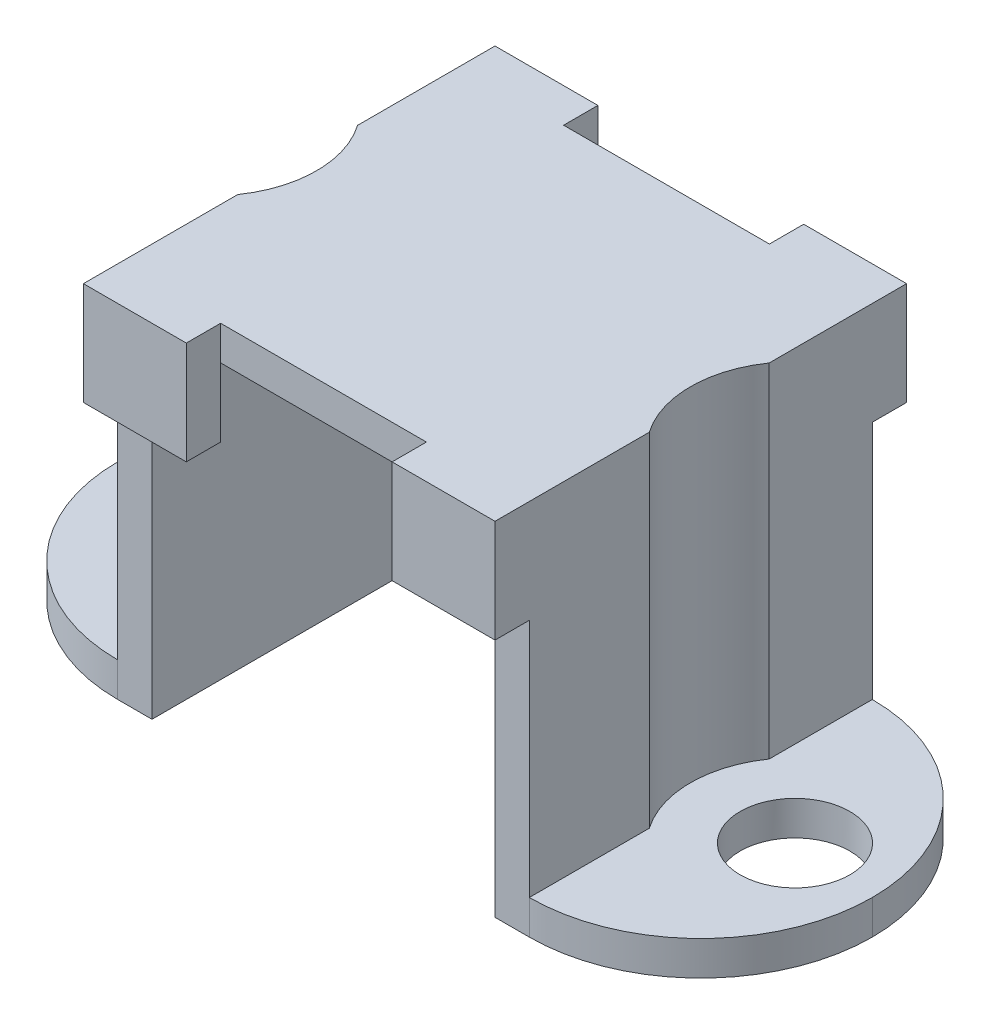
SolidWorks part; units mm, degrees
ref_plane "Front Plane" through (0, 0, 0) normal (0, 0, 1) x (1, 0, 0)
ref_plane "Top Plane" through (0, 0, 0) normal (0, 1, 0) x (1, 0, 0)
ref_plane "Right Plane" through (0, 0, 0) normal (1, 0, 0) x (0, 0, -1)
sketch "Sketch1" plane through (0, 0, 0) normal (0, 1, 0) x (1, 0, 0)
  line L5 (0, 5) -> (6, 5)
  line L6 (0, 5) -> (0, -5)
  line L7 (0, -5) -> (6, -5)
  line L8 (6, 5) -> (6, -5)
  point P4 (0, 0)
  dimension "D1" = 10
  dimension "D2" = 6
extrude "Boss-Extrude1" add sketch "Sketch1" along normal blind 1
sketch "Sketch2" plane through (0, 0, 0) normal (0, -1, 0) x (1, 0, 0)
  line L0 (0, 5) -> (6, 5) construction
  line L1 (6, -5) -> (5, -5)
  line L2 (6, -5) -> (6, 5)
  line L3 (6, 5) -> (5, 5)
  line L4 (5, -5) -> (5, 5)
  dimension "D1" = 1
extrude "Boss-Extrude2" add sketch "Sketch2" along normal blind 10
sketch "Sketch3" plane through (6, 0, 0) normal (1, 0, 0) x (0, 0, -1)
  line L0 (5, 1) -> (5, -10) construction
  line L1 (-5, -10) -> (5, -10)
  line L2 (-5, -10) -> (-5, -9)
  line L3 (-5, -9) -> (5, -9)
  line L4 (5, -10) -> (5, -9)
  dimension "D1" = 1
extrude "Boss-Extrude3" add sketch "Sketch3" along normal blind 5
sketch "Sketch4" plane through (0, -9, 0) normal (0, 1, 0) x (1, 0, 0)
  line L0 (11, -5) -> (5, -5) construction
  line L1 (5, -5) -> (5, 5) construction
  circle A0 centre (8.5, 0.2466) radius 1.6
  dimension "D1" = 3.2
  dimension "D2" = 5.2466
  dimension "D3" = 3.5
extrude "Cut-Extrude1" cut sketch "Sketch4" against normal up to next
sketch "Sketch5" plane through (0, 1, 0) normal (0, 1, 0) x (1, 0, 0)
  circle A0 centre (8.5, 0.2466) radius 3.05
  dimension "D1" = 6.1
extrude "Cut-Extrude6" cut sketch "Sketch5" against normal up to vertex (10 mm away) up to point (6, -9, -5)
sketch "Sketch6" plane through (0, 0, -5) normal (0, 0, -1) x (-1, 0, 0)
  line L1 (-3, -2) -> (-6, -2)
  line L2 (-3, -2) -> (-3, 1)
  line L3 (-3, 1) -> (-6, 1)
  line L4 (-6, -2) -> (-6, 1)
  line L5 (-3, -2) -> (-6, 1) construction
  line L6 (-3, 1) -> (-6, -2) construction
  point P0 (-4.5, -0.5)
  dimension "D1" = 3
extrude "Boss-Extrude4" add sketch "Sketch6" along normal blind 1
sketch "Sketch7" plane through (0, 0, 5) normal (0, 0, 1) x (1, 0, 0)
  line L1 (3, -2) -> (6, -2)
  line L2 (3, -2) -> (3, 1)
  line L3 (3, 1) -> (6, 1)
  line L4 (6, -2) -> (6, 1)
  line L5 (3, -2) -> (6, 1) construction
  line L6 (3, 1) -> (6, -2) construction
  point P0 (4.5, -0.5)
  dimension "D1" = 3
extrude "Boss-Extrude5" add sketch "Sketch7" along normal blind 1
fillet "Fillet2" radius 5 2 edges at (11, -9.5, 5) (11, -9.5, -5)
mirror "Mirror1" about plane through (0, 0, 0) normal (1, 0, 0) of bodies 108
